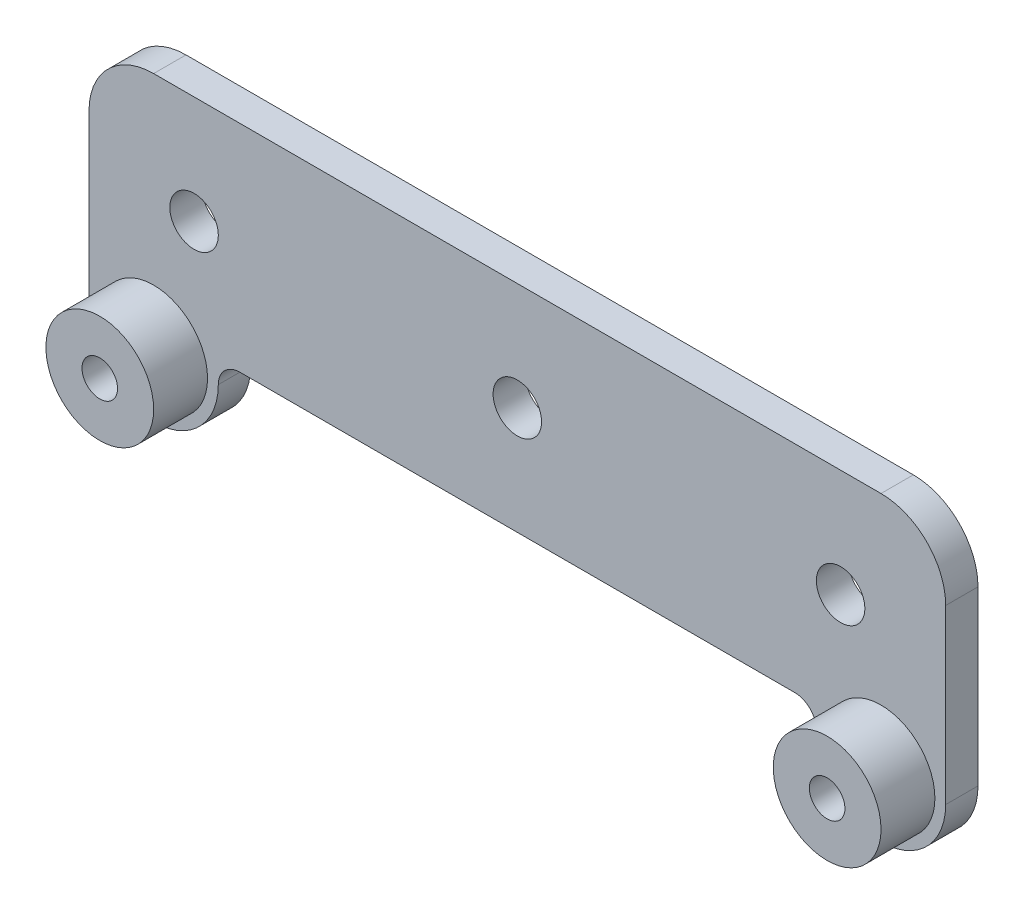
SolidWorks part; units mm, degrees
material "ABS"
ref_plane "前基準面" through (0, 0, 0) normal (0, 0, 1) x (1, 0, 0)
ref_plane "上基準面" through (0, 0, 0) normal (0, 1, 0) x (1, 0, 0)
ref_plane "右基準面" through (0, 0, 0) normal (1, 0, 0) x (0, 0, -1)
sketch "草圖1" plane through (0, 0, 0) normal (0, 0, 1) x (1, 0, 0)
  line L0 (-33.75, 10) -> (33.75, 10)
  line L5 (39.75, 4) -> (39.75, -12)
  line L8 (25.75, -10) -> (-25.75, -10)
  line L11 (-39.75, -12) -> (-39.75, 4)
  line L12 (0, -10) -> (0, 10) construction
  line L13 (-33.75, -12) -> (33.75, -12) construction
  arc A0 (-39.75, -12) -> (-27.75, -12) centre (-33.75, -12) ccw
  arc A1 (27.75, -12) -> (39.75, -12) centre (33.75, -12) ccw
  arc A2 (33.75, 10) -> (39.75, 4) centre (33.75, 4) cw
  arc A3 (-33.75, 10) -> (-39.75, 4) centre (-33.75, 4) ccw
  arc A4 (27.75, -12) -> (25.75, -10) centre (25.75, -12) ccw
  arc A5 (-25.75, -10) -> (-27.75, -12) centre (-25.75, -12) ccw
  point P5 (0, 0)
  point P14 (-19.75, -10)
  dimension "D3" = 6
  dimension "D1" = 20
  dimension "D2" = 67.5
  dimension "D4" = 12
extrude "填料-伸長1" add sketch "草圖1" along normal blind 3
sketch "草圖4" plane through (0, 0, 3) normal (0, 0, 1) x (1, 0, 0)
  circle A0 centre (-33.75, -12) radius 5
  circle A1 centre (33.75, -12) radius 5
  dimension "D1" = 10
extrude "填料-伸長2" add sketch "草圖4" along normal blind 5
hole_wizard "M4x0.7 螺紋孔1" positions "草圖5" profile "草圖6" tap size "M4x0.7" standard "Ansi Metric" end condition through all
sketch "草圖5" plane through (0, 0, 8) normal (0, 0, 1) x (1, 0, 0)
  point P0 (-33.75, -12)
  point P3 (33.75, -12)
sketch "草圖6" plane through (-33.75, -12, 8) normal (1, 0, 0) x (0, -1, 0)
  line L0 (0, 0) -> (0, 8)
  line L1 (0, 8) -> (1.65, 8)
  line L2 (1.65, 8) -> (1.65, 0)
  line L5 (1.65, 0) -> (0, 0)
  line L11 (0, -6.35) -> (0, 107.95) construction
  dimension "貫穿螺孔鑽直徑" = 3.3
  dimension "貫穿螺孔鑽深度" = 8
hole_wizard "M4 餘隙孔1" positions "草圖7" profile "草圖8" hole size "M4" standard "Ansi Metric" end condition through all
sketch "草圖7" plane through (0, 0, 3) normal (0, 0, 1) x (1, 0, 0)
  line L0 (-30, 0) -> (30, 0) construction
  point P1 (-30, 0)
  point P2 (30, 0)
  point P10 (0, 0)
  dimension "D1" = 60
sketch "草圖8" plane through (-30, 0, 3) normal (1, 0, 0) x (0, -1, 0)
  line L0 (0, 0) -> (0, 3)
  line L1 (0, 3) -> (2.25, 3)
  line L2 (2.25, 3) -> (2.25, 0)
  line L5 (2.25, 0) -> (0, 0)
  line L11 (0, -6.35) -> (0, 107.95) construction
  dimension "貫穿孔直徑" = 4.5
  dimension "貫穿孔深度" = 3
equation "\"ˇ\"=3"
